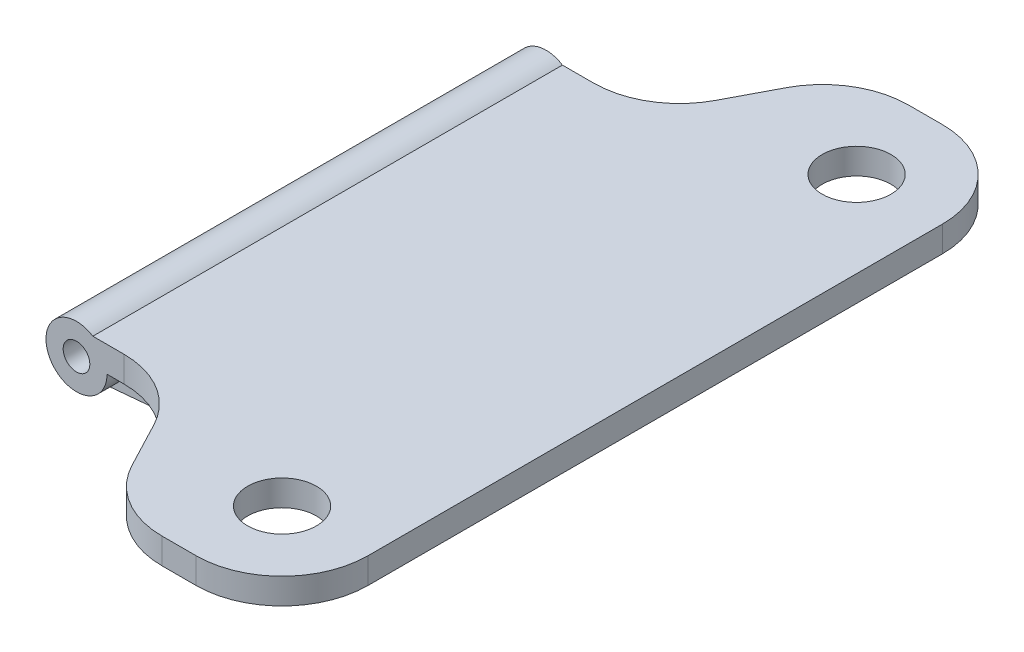
SolidWorks part; units mm, degrees
ref_plane "Front Plane" through (0, 0, 0) normal (0, 0, 1) x (1, 0, 0)
ref_plane "Top Plane" through (0, 0, 0) normal (0, 1, 0) x (1, 0, 0)
ref_plane "Right Plane" through (0, 0, 0) normal (1, 0, 0) x (0, 0, -1)
sketch "Sketch1" plane through (0, 0, 0) normal (0, 0, 1) x (1, 0, 0)
  circle A0 centre (0, 0) radius 1.9685
  circle A1 centre (0, 0) radius 4.5085
  dimension "D1" = 3.937
  dimension "D2" = 2.54
extrude "Mount Cylinder" add sketch "Sketch1" along normal blind 34.671 and the other way blind 34.671
sketch "Sketch2" plane through (0, 0, 0) normal (0, 1, 0) x (1, 0, 0)
  line L0 (0, 0) -> (75.1051, 0) construction
  line L1 (38.1, 42.418) -> (38.1, -42.418) construction
  line L2 (1.9685, -34.671) -> (1.9685, 34.671) construction
  line L4 (1.9685, -34.671) -> (6.9911, -34.671)
  line L5 (18.2364, -41.469) -> (21.8321, -48.32)
  line L6 (33.0774, -55.118) -> (38.1, -55.118)
  line L7 (50.8, -42.418) -> (50.8, 42.418)
  line L8 (1.9685, -34.671) -> (1.9685, 34.671)
  line L9 (33.0774, 55.118) -> (38.1, 55.118)
  line L10 (18.2364, 41.469) -> (21.8321, 48.32)
  line L11 (1.9685, 34.671) -> (6.9911, 34.671)
  circle A0 centre (38.1, 42.418) radius 5.08
  circle A1 centre (38.1, -42.418) radius 5.08
  arc A2 (38.1, -55.118) -> (50.8, -42.418) centre (38.1, -42.418) ccw
  arc A3 (21.8321, -48.32) -> (33.0774, -55.118) centre (33.0774, -42.418) ccw
  arc A4 (6.9911, -34.671) -> (18.2364, -41.469) centre (6.9911, -47.371) cw
  arc A5 (38.1, 55.118) -> (50.8, 42.418) centre (38.1, 42.418) cw
  arc A6 (21.8321, 48.32) -> (33.0774, 55.118) centre (33.0774, 42.418) cw
  arc A7 (6.9911, 34.671) -> (18.2364, 41.469) centre (6.9911, 47.371) ccw
  point P6 (38.1, 0)
  point P12 (1.9685, 0)
  point P20 (0, 0)
  point P22 (50.8, -55.118)
  point P25 (25.4, -55.118)
  point P28 (14.6685, -34.671)
  point P30 (50.8, 0)
  point P37 (1.9685, 0)
  dimension "D2" = 10.16
  dimension "D8" = 12.7
  dimension "D1" = 84.836
  dimension "D3" = 12.7
  dimension "D4" = 12.7
  dimension "D5" = 12.7
  dimension "D6" = 38.1
  dimension "D7" = 25.4
extrude "Boss-Extrude1" add sketch "Sketch2" along normal blind 3.81
sketch "Sketch3" plane through (0, 0, 0) normal (0, 0, 1) x (1, 0, 0)
  line L0 (0, -4.5085) -> (0, -1.9685)
  line L1 (0, -1.9685) -> (4.0561, -1.9685)
  line L2 (4.0561, -1.9685) -> (4.0561, 0)
  line L3 (4.0561, 0) -> (50.8, 0)
  line L4 (50.8, 0) -> (0, -4.5085)
  arc A0 (2.4105, 3.81) -> (4.5085, 0) centre (0, 0) ccw construction
  circle A1 centre (0, 0) radius 1.9685 construction
extrude "Boss-Extrude3" add sketch "Sketch3" along normal mid plane 63.5 contours L4 L0 L1 L2 L3
